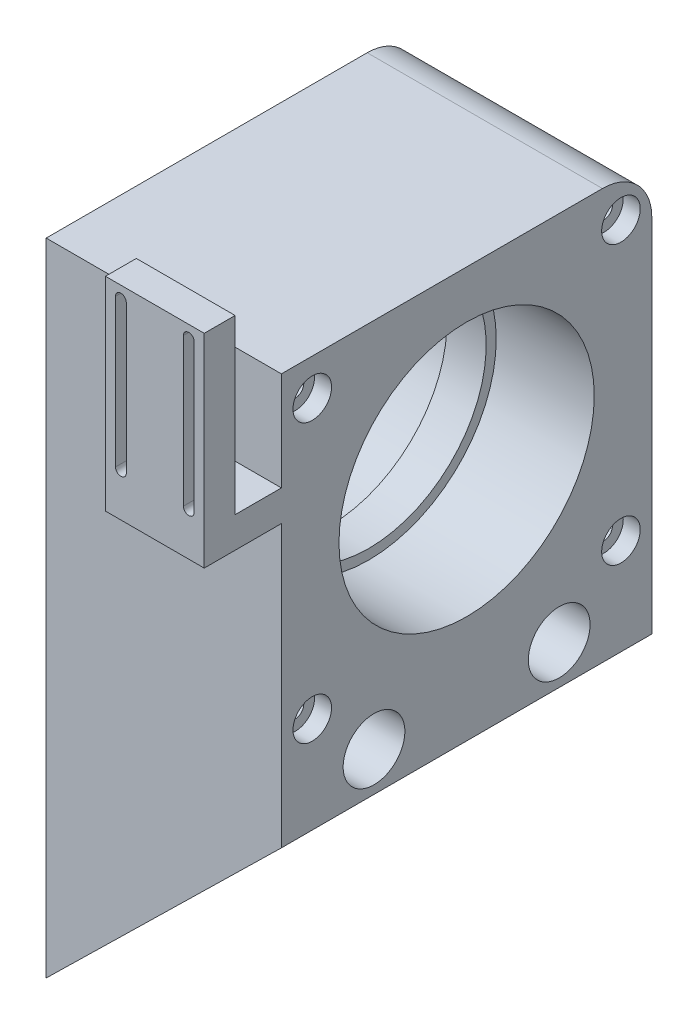
SolidWorks part; units mm, degrees
ref_plane "Front Plane" through (0, 0, 0) normal (0, 0, 1) x (1, 0, 0)
ref_plane "Top Plane" through (0, 0, 0) normal (0, 1, 0) x (1, 0, 0)
ref_plane "Right Plane" through (0, 0, 0) normal (1, 0, 0) x (0, 0, -1)
sketch "Sketch1" plane through (0, 0, 0) normal (0, 0, 1) x (1, 0, 0)
  line L0 (381, 457.2) -> (457.2, 457.2)
  line L1 (457.2, 457.2) -> (457.2, 431.8)
  line L2 (381, 457.2) -> (381, 357.2)
  line L5 (381, 357.2) -> (457.2, 431.8)
  dimension "D1" = 76.2
  dimension "D2" = 100
extrude "Boss-Extrude1" add sketch "Sketch1" along normal blind 120
sketch "Sketch3" plane through (457.2, 0, 0) normal (1, 0, 0) x (0, 0, -1)
  line L1 (-120, 431.8) -> (0, 431.8)
  line L2 (-120, 431.8) -> (-120, 357.2)
  line L3 (-120, 357.2) -> (0, 357.2)
  line L4 (0, 431.8) -> (0, 357.2)
  circle A0 centre (-90, 394.5) radius 4.25
  circle A1 centre (-30, 394.5) radius 4.25
  circle A2 centre (-90, 444.5) radius 4.25
  circle A3 centre (-30, 444.5) radius 4.25
  dimension "D1" = 30
  dimension "D2" = 30
  dimension "D3" = 37.3
  dimension "D4" = 37.3
extrude "Cut-Extrude1" cut sketch "Sketch3" against normal blind 120 contours A1 | A0
sketch "Sketch5" plane through (457.2, 0, 0) normal (1, 0, 0) x (0, 0, -1)
  circle A0 centre (-90, 394.5) radius 10
  circle A1 centre (-30, 394.5) radius 10
  circle A2 centre (-90, 444.5) radius 10
  circle A3 centre (-30, 444.5) radius 10
extrude "Cut-Extrude2" cut sketch "Sketch5" against normal blind 53
sketch "Sketch6" plane through (457.2, 0, 0) normal (1, 0, 0) x (0, 0, -1)
  circle A0 centre (-90, 444.5) radius 4.25
  circle A1 centre (-30, 444.5) radius 4.25
extrude "Cut-Extrude3" cut sketch "Sketch6" against normal blind 103
sketch "Sketch7" plane through (0, 457.2, 0) normal (0, 1, 0) x (1, 0, 0)
  line L1 (381, 0) -> (457.2, 0)
  line L2 (381, 0) -> (381, -120)
  line L3 (381, -120) -> (457.2, -120)
  line L4 (457.2, 0) -> (457.2, -120)
extrude "Boss-Extrude2" add sketch "Sketch7" along normal blind 101.6
sketch "Sketch8" plane through (381, 0, 0) normal (-1, 0, 0) x (0, 0, 1)
  line L0 (120, 457.2) -> (0, 457.2)
  line L1 (120, 558.8) -> (120, 357.2) construction
  line L2 (0, 558.8) -> (0, 357.2) construction
  line L3 (0, 558.8) -> (120, 558.8) construction
  circle A0 centre (60, 508) radius 41.35
  dimension "D1" = 101.6
  dimension "D2" = 50.8
extrude "Cut-Extrude4" cut sketch "Sketch8" against normal blind 31.75 contours A0 region at (381, 508, 60)
sketch "Sketch9" plane through (457.2, 0, 0) normal (1, 0, 0) x (0, 0, -1)
  line L0 (-120, 558.8) -> (0, 558.8) construction
  line L1 (-120, 431.8) -> (-120, 558.8) construction
  circle A0 centre (-60, 508) radius 41.35
  dimension "D1" = 50.8
  dimension "D2" = 60
extrude "Cut-Extrude5" cut sketch "Sketch9" against normal blind 31.75
sketch "Sketch10" plane through (457.2, 0, 0) normal (1, 0, 0) x (0, 0, -1)
  circle A0 centre (-60, 508) radius 38.1
extrude "Cut-Extrude6" cut sketch "Sketch10" against normal blind 76.2
sketch "Sketch13" plane through (0, 558.8, 0) normal (0, 1, 0) x (1, 0, 0)
  line L1 (381, 0) -> (457.2, 0)
  line L2 (381, 0) -> (381, -120)
  line L3 (381, -120) -> (457.2, -120)
  line L4 (457.2, 0) -> (457.2, -120)
extrude "Boss-Extrude3" add sketch "Sketch13" along normal blind 6
sketch "Sketch11" plane through (457.2, 0, 0) normal (1, 0, 0) x (0, 0, -1)
  line L0 (-120, 431.8) -> (-120, 564.8) construction
  line L1 (-110, 553) -> (-10, 553)
  line L2 (-110, 553) -> (-110, 463)
  line L3 (-110, 463) -> (-10, 463)
  line L4 (-10, 553) -> (-10, 463)
  line L5 (0, 431.8) -> (0, 564.8) construction
  circle A0 centre (-60, 508) radius 5.3331
  circle A1 centre (-110, 553) radius 2.75
  circle A2 centre (-10, 553) radius 2.75
  circle A3 centre (-10, 463) radius 2.75
  circle A4 centre (-110, 463) radius 2.75
  dimension "D1" = 10
  dimension "D2" = 10
  dimension "D3" = 45
  dimension "D4" = 90
extrude "Cut-Extrude7" cut sketch "Sketch11" against normal blind 84.4 contours L1 A1 L2 | L2 A1 L1 | L4 A2 L1 | L1 A2 L4 | L3 A3 L4 | L4 A3 L3 | L2 A4 L3 | L3 A4 L2 region at (457.2, 553.389, 110.389) region at (457.2, 551.8329, 108.8329) region at (457.2, 553.389, 9.611) region at (457.2, 551.8329, 11.1671) region at (457.2, 464.1671, 108.8329) region at (457.2, 462.611, 110.389) region at (457.2, 462.611, 9.611) region at (457.2, 464.1671, 11.1671)
sketch "Sketch12" plane through (457.2, 0, 0) normal (1, 0, 0) x (0, 0, -1)
  circle A0 centre (-110, 553) radius 6.25
  circle A1 centre (-10, 553) radius 6.25
  circle A2 centre (-10, 463) radius 6.25
  circle A3 centre (-110, 463) radius 6.25
extrude "Cut-Extrude8" cut sketch "Sketch12" against normal blind 5.5
fillet "Fillet1" radius 16 1 edges at (419.1, 564.8, 0)
sketch "Sketch17" plane through (0, 0, 120) normal (0, 0, 1) x (1, 0, 0)
  line L5 (428.45, 592.8) -> (428.45, 568.8)
  line L6 (457.2, 564.8) -> (425.2, 564.8)
  line L7 (457.2, 564.8) -> (457.2, 596.8)
  line L8 (457.2, 596.8) -> (425.2, 596.8)
  line L9 (425.2, 564.8) -> (425.2, 596.8)
  line L10 (431.95, 568.8) -> (431.95, 592.8)
  line L11 (450.45, 592.8) -> (450.45, 568.8)
  line L12 (453.95, 592.8) -> (453.95, 568.8)
  circle A4 centre (430.2, 592.8) radius 1.75
  circle A6 centre (430.2, 568.8) radius 1.75
  circle A7 centre (452.2, 568.8) radius 1.75
  circle A8 centre (452.2, 592.8) radius 1.75
  dimension "D3" = 22
  dimension "D1" = 32
  dimension "D2" = 32
  dimension "D4" = 22
  dimension "D5" = 5
  dimension "D6" = 5
  dimension "D7" = 4
  dimension "D8" = 4
  dimension "D9" = 4
  dimension "D10" = 4
sketch "Sketch18" plane through (0, 0, 120) normal (0, 0, 1) x (1, 0, 0)
  line L0 (457.2, 431.8) -> (457.2, 564.8) construction
  line L1 (457.2, 522.8) -> (425.2, 522.8)
  line L2 (457.2, 522.8) -> (457.2, 532.8)
  line L3 (457.2, 532.8) -> (425.2, 532.8)
  line L4 (425.2, 522.8) -> (425.2, 532.8)
  line L6 (381, 564.8) -> (457.2, 564.8) construction
  dimension "D1" = 32
  dimension "D2" = 32
  dimension "D3" = 10
extrude "Boss-Extrude6" add sketch "Sketch18" along normal blind 15
sketch "Sketch20" plane through (0, 0, 135) normal (0, 0, 1) x (1, 0, 0)
  line L0 (431.95, 584.6825) -> (431.95, 536.8)
  line L2 (425.2, 532.8) -> (425.2, 588.6825)
  line L3 (425.2, 588.6825) -> (457.2, 588.6825)
  line L4 (457.2, 536.6825) -> (457.2, 588.6825)
  line L5 (428.45, 584.6825) -> (428.45, 536.8)
  line L6 (450.45, 584.6825) -> (450.45, 536.8)
  line L7 (450.45, 584.6825) -> (450.45, 536.8)
  line L8 (425.2, 532.8) -> (425.2, 522.8)
  line L9 (425.2, 522.8) -> (457.2, 522.8)
  line L10 (457.2, 522.8) -> (457.2, 536.6825)
  line L11 (453.95, 584.6825) -> (453.95, 536.8)
  circle A0 centre (430.2, 584.6825) radius 1.75
  circle A1 centre (452.2, 584.6825) radius 1.75
  circle A2 centre (452.2, 536.8) radius 1.75
  circle A3 centre (430.2, 536.8) radius 1.75
  point P20 (428.45, 536.8)
  line M6 (457.2, 522.8) -> (457.2, 532.8)
  line M7 (457.2, 532.8) -> (425.2, 532.8)
  line M8 (425.2, 532.8) -> (425.2, 522.8)
  line M9 (425.2, 522.8) -> (457.2, 522.8)
  dimension "D1" = 22
  dimension "D2" = 22
  dimension "D3" = 5
  dimension "D4" = 52
  dimension "D5" = 4
  dimension "D6" = 5
  dimension "D7" = 4
extrude "Boss-Extrude7" add sketch "Sketch20" along normal blind 10 contours L4 L3 L2 A3 L5 A0 L0 A2 L6 A1 L7 M7 | M9 M6 M7 M8 region at (441.2, 527.8, 135) region at (441.2, 560.7413, 135)
